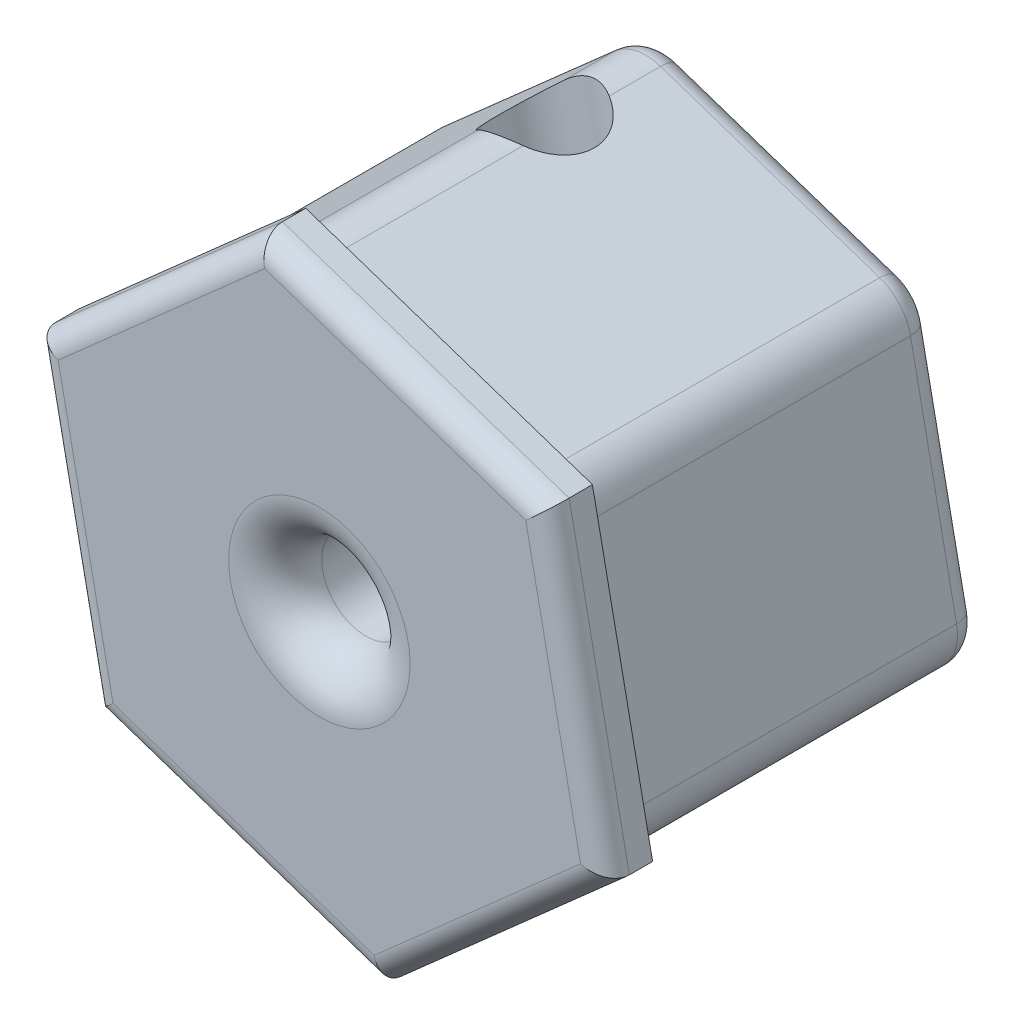
SolidWorks part; units mm, degrees
ref_plane "Płaszczyzna przednia" through (0, 0, 0) normal (0, 0, 1) x (1, 0, 0)
ref_plane "Płaszczyzna górna" through (0, 0, 0) normal (0, 1, 0) x (1, 0, 0)
ref_plane "Płaszczyzna prawa" through (0, 0, 0) normal (1, 0, 0) x (0, 0, -1)
sketch "Szkic1" plane through (0, 0, 0) normal (0, 0, 1) x (1, 0, 0)
  line L7 (1.7831, -4.5641) -> (-0.6537, 7.4307)
  line L8 (-0.6537, 7.4307) -> (-12.2599, 11.3178)
  line L9 (-12.2599, 11.3178) -> (-21.4293, 3.2101)
  line L10 (-21.4293, 3.2101) -> (-18.9925, -8.7847)
  line L11 (-18.9925, -8.7847) -> (-7.3863, -12.6718)
  line L12 (-7.3863, -12.6718) -> (1.7831, -4.5641)
  circle A0 centre (-9.8231, -0.677) radius 10.6 construction
  dimension "D1" = 21.2
extrude "Dodanie-wyciągnięcie1" add sketch "Szkic1" along normal blind 17
fillet "Zaokrąglenie1" radius 2 6 edges at (-0.6537, 7.4307, 8.5) (1.7831, -4.5641, 8.5) (-7.3863, -12.6718, 8.5) (-18.9925, -8.7847, 8.5) (-21.4293, 3.2101, 8.5) (-12.2599, 11.3178, 8.5)
sketch "Szkic3" plane through (0, 0, 17) normal (0, 0, 1) x (1, 0, 0)
  line L0 (-21.1995, 2.0785) -> (1.5532, -3.4325) construction
  line L1 (-13.125, 10.5529) -> (-6.5213, -11.9069) construction
  line L2 (1.5532, -3.4325) -> (-0.4238, 6.2991) construction
  line L3 (-0.0915, 7.9279) -> (-12.4094, 12.0533)
  line L4 (-12.4094, 12.0533) -> (-22.141, 3.4484)
  line L5 (-22.141, 3.4484) -> (-19.5548, -9.2819)
  line L6 (-19.5548, -9.2819) -> (-7.2369, -13.4074)
  line L7 (-7.2369, -13.4074) -> (2.4948, -4.8025)
  line L8 (2.4948, -4.8025) -> (-0.0915, 7.9279)
  circle A0 centre (-9.8231, -0.677) radius 11.25 construction
  dimension "D1" = 0
  dimension "D2" = 22.5
extrude "Dodanie-wyciągnięcie2" add sketch "Szkic3" against normal blind 2
fillet "Zaokrąglenie2" radius 1 12 edges at (-0.8855, 7.2258, 0) (0.5647, 1.4333, 0) (1.4897, -4.4658, 0) (-2.8016, -8.618, 0) (-7.4479, -12.3686, 0) (-13.1894, -10.7283, 0) (-18.7608, -8.5798, 0) (-20.2109, -2.7873, 0) (-21.136, 3.1118, 0) (-16.8446, 7.2639, 0) (-12.1983, 11.0146, 0) (-6.4568, 9.3743, 0)
ref_plane "Płaszczyzna1" through (-9.5659, -1.9433, 0) normal (0.98, 0.1991, 0) x (0, 0, -1)
ref_plane "Płaszczyzna2" through (-0.2573, 1.2663, 0) normal (-0.1991, 0.98, 0) x (0.98, 0.1991, 0)
fillet "Zaokrąglenie3" radius 1 6 edges at (-2.3711, -9.1049, 17) (-13.3959, -11.3446, 17) (-20.8479, -2.9168, 17) (-17.2752, 7.7509, 17) (-6.2504, 9.9906, 17) (1.2017, 1.5627, 17)
sketch "Szkic4" plane through (-0.2573, 1.2663, 0) normal (-0.1991, 0.98, 0) x (0.98, 0.1991, 0)
  line L0 (-9.7613, -10.9512) -> (-9.7613, 10.9512) construction
  line L2 (1.4887, -15) -> (-9.7613, -15) construction
  circle A0 centre (-9.7613, -5.05) radius 2.1
  dimension "D1" = 0
  dimension "D3" = 4.2
  dimension "D2" = 9.95
extrude "Wytnij-wyciągnięcie1" cut sketch "Szkic4" against normal through all both and the other way through all
sketch "Szkic5" plane through (0, 0, 17) normal (0, 0, 1) x (1, 0, 0)
  line L0 (-18.5833, 4.1439) -> (-3.6386, 7.18)
  line L1 (-16.4743, -6.2375) -> (-1.5295, -3.2014)
  line L5 (-1.5295, -3.2014) -> (-3.6386, 7.18)
  line L8 (-7.3856, -12.6753) -> (-11.7461, 8.7886) construction
  line L9 (-16.4743, -6.2375) -> (-18.5833, 4.1439)
sketch "Szkic9" plane through (-0.2573, 1.2663, 0) normal (-0.1991, 0.98, 0) x (0.98, 0.1991, 0)
  circle A0 centre (-9.7613, -5.05) radius 2.1
extrude "Dodanie-wyciągnięcie3" add sketch "Szkic9" along normal blind 6 and the other way blind 6
sketch "Szkic8" plane through (0, 0, 17) normal (0, 0, 1) x (1, 0, 0)
  line L0 (-12.1795, 10.9217) -> (-7.4668, -12.2758) construction
  line L1 (-0.9565, 7.163) -> (-18.6898, -8.517) construction
  circle A0 centre (-9.8231, -0.677) radius 1.9
extrude "Wytnij-wyciągnięcie3" cut sketch "Szkic8" against normal blind 10.5
fillet "Zaokrąglenie5" radius 2 1 edges at (-7.9231, -0.677, 17)
sketch "Szkic11" plane through (0, 0, 0) normal (0, 0, -1) x (-1, 0, 0)
  line L0 (20.2195, 2.2776) -> (6.0084, -2.3764) construction
  line L1 (18.2424, -7.4541) -> (6.8207, 1.6218) construction
  line L2 (13.832, 1.978) -> (12.4782, -4.6859)
  line L3 (18.2424, -7.4541) -> (20.2195, 2.2776) construction
  line L5 (7.1681, 3.3318) -> (5.8143, -3.3321)
  line L6 (12.4782, -4.6859) -> (5.8143, -3.3321)
  line L8 (13.832, 1.978) -> (7.1681, 3.3318)
  dimension "D1" = 360
extrude "Wytnij-wyciągnięcie4" cut sketch "Szkic11" against normal up to surface (6.5 mm away) up to face at (-7.9231, -0.677, 6.5)
sketch "Szkic12" plane through (0, 0, 0) normal (0, 0, -1) x (-1, 0, 0)
  circle A0 centre (13.832, 1.978) radius 0.75
  circle A1 centre (12.4782, -4.6859) radius 0.75
  circle A2 centre (5.8143, -3.3321) radius 0.75
  circle A3 centre (7.1681, 3.3318) radius 0.75
  dimension "D1" = 1.5
  dimension "D2" = 1.5
  dimension "D3" = 1.5
  dimension "D4" = 1.5
extrude "Wytnij-wyciągnięcie5" cut sketch "Szkic12" against normal up to surface (6.5 mm away) up to face at (-7.9231, -0.677, 6.5)
